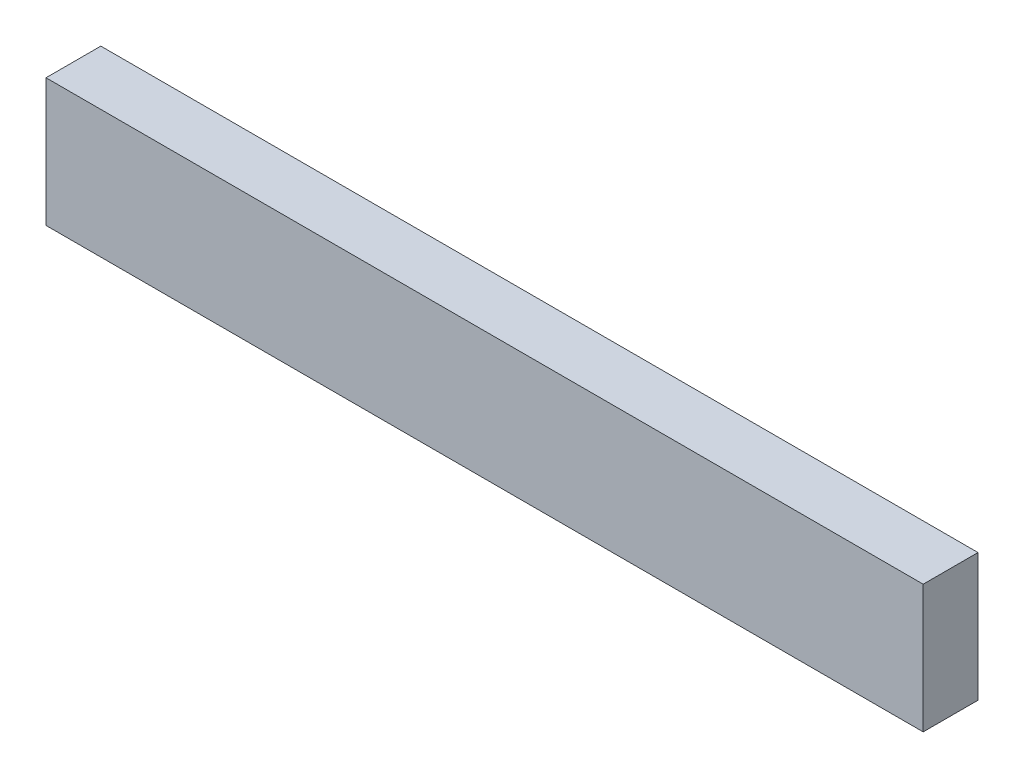
SolidWorks part; units mm, degrees
material "Cedar"
ref_plane "Front Plane" through (0, 0, 0) normal (0, 0, 1) x (1, 0, 0)
ref_plane "Top Plane" through (0, 0, 0) normal (0, 1, 0) x (1, 0, 0)
ref_plane "Right Plane" through (0, 0, 0) normal (1, 0, 0) x (0, 0, -1)
sketch "Sketch3" plane through (0, 0, 0) normal (1, 0, 0) x (0, 0, -1)
  line L1 (-19.05, -44.45) -> (19.05, -44.45)
  line L2 (-19.05, -44.45) -> (-19.05, 44.45)
  line L3 (-19.05, 44.45) -> (19.05, 44.45)
  line L4 (19.05, -44.45) -> (19.05, 44.45)
  line L5 (-19.05, -44.45) -> (19.05, 44.45) construction
  line L6 (-19.05, 44.45) -> (19.05, -44.45) construction
  point P0 (0, 0)
  dimension "D1" = 38.1
  dimension "D2" = 88.9
extrude "Boss-Extrude1" add sketch "Sketch3" along normal blind 304.8 and the other way blind 304.8
